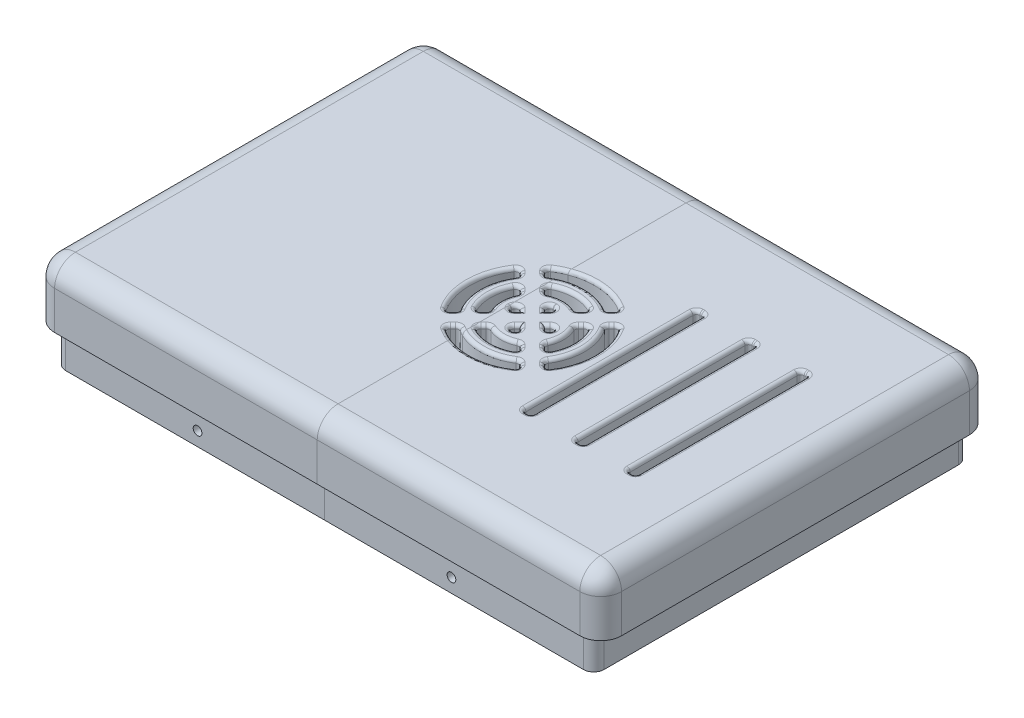
SolidWorks part; units mm, degrees
ref_plane "Plan de face" through (0, 0, 0) normal (0, 0, 1) x (1, 0, 0)
ref_plane "Plan de dessus" through (0, 0, 0) normal (0, 1, 0) x (1, 0, 0)
ref_plane "Plan de droite" through (0, 0, 0) normal (1, 0, 0) x (0, 0, -1)
sketch "Esquisse1" plane through (0, 0, 0) normal (0, 1, 0) x (1, 0, 0)
  line L1 (-81.5, 56) -> (81.5, 56)
  line L2 (-81.5, 56) -> (-81.5, -56)
  line L3 (-81.5, -56) -> (81.5, -56)
  line L4 (81.5, 56) -> (81.5, -56)
  line L5 (-81.5, 56) -> (81.5, -56) construction
  line L6 (-81.5, -56) -> (81.5, 56) construction
  point P0 (0, 0)
  dimension "D1" = 112
  dimension "D2" = 163
extrude "General shape" add sketch "Esquisse1" along normal blind 7
sketch "Esquisse2" plane through (0, 0, 0) normal (0, -1, 0) x (1, 0, 0)
  line L1 (81.5, -56) -> (-81.5, -56)
  line L2 (81.5, -56) -> (81.5, 56)
  line L3 (81.5, 56) -> (-81.5, 56)
  line L4 (-81.5, -56) -> (-81.5, 56)
  line L5 (81.5, -56) -> (-81.5, 56) construction
  line L6 (81.5, 56) -> (-81.5, -56) construction
  line L7 (73.5, -51.5) -> (-73.5, -51.5)
  line L8 (73.5, -51.5) -> (73.5, 51.5)
  line L9 (73.5, 51.5) -> (-73.5, 51.5)
  line L10 (-73.5, -51.5) -> (-73.5, 51.5)
  line L11 (73.5, -51.5) -> (-73.5, 51.5) construction
  line L12 (73.5, 51.5) -> (-73.5, -51.5) construction
  point P0 (0, 0)
  point P7 (0, 0)
  dimension "D1" = 8
  dimension "D2" = 4.5
extrude "Boss.-Extru.2" add sketch "Esquisse2" along normal blind 20
sketch "Esquisse3" plane through (0, -20, 0) normal (0, -1, 0) x (-1, 0, 0)
  line L1 (-81.5, 56) -> (81.5, 56)
  line L2 (-81.5, 56) -> (-81.5, -56)
  line L3 (-81.5, -56) -> (81.5, -56)
  line L4 (81.5, 56) -> (81.5, -56)
  line L5 (-81.5, 56) -> (81.5, -56) construction
  line L6 (-81.5, -56) -> (81.5, 56) construction
  line L7 (-77.4, 53.9) -> (77.4, 53.9)
  line L8 (-77.4, 53.9) -> (-77.4, -53.9)
  line L9 (-77.4, -53.9) -> (77.4, -53.9)
  line L10 (77.4, 53.9) -> (77.4, -53.9)
  line L11 (-77.4, 53.9) -> (77.4, -53.9) construction
  line L12 (-77.4, -53.9) -> (77.4, 53.9) construction
  point P0 (0, 0)
  point P7 (0, 0)
  dimension "D1" = 2.1
  dimension "D2" = 4.1
extrude "Enlèv. mat.-Extru.1" cut sketch "Esquisse3" against normal blind 10
fillet "Fillet1" radius 6 4 edges at (81.5, -1.5, 56) (81.5, -1.5, -56) (-81.5, -1.5, -56) (-81.5, -1.5, 56)
fillet "Fillet2" radius 6 8 edges at (-79.7426, 7, 54.2426) (-81.5, 7, 0) (-79.7426, 7, -54.2426) (0, 7, -56) (79.7426, 7, -54.2426) (81.5, 7, 0) (79.7426, 7, 54.2426) (0, 7, 56)
fillet "Fillet3" radius 3 4 edges at (73.5, 0, 0) (0, 0, -51.5) (-73.5, 0, 0) (0, 0, 51.5)
fillet "Fillet4" radius 3 4 edges at (-77.4, -15, 53.9) (77.4, -15, 53.9) (77.4, -15, -53.9) (-77.4, -15, -53.9)
sketch "Esquisse4" plane through (0, 0, 0) normal (0, -1, 0) x (1, 0, 0)
  line L0 (6.5, 0.67) -> (-6.2279, 13.3979) construction
  line L1 (-73, -51) -> (73, -51)
  line L2 (-73, -51) -> (-73, 51)
  line L3 (-73, 51) -> (73, 51)
  line L4 (73, -51) -> (73, 51)
  line L5 (-73, -51) -> (73, 51) construction
  line L6 (-73, 51) -> (73, -51) construction
  line L7 (-2.5, 0.67) -> (-5.5, 0.67) construction
  line L8 (-5.5, 0.67) -> (-8.5, 0.67) construction
  line L9 (-8.5, 0.67) -> (-11.5, 0.67) construction
  line L10 (-2.5, 0.67) -> (0.5, 0.67) construction
  line L11 (0.5, 0.67) -> (3.5, 0.67) construction
  line L12 (3.5, 0.67) -> (6.5, 0.67) construction
  line L13 (6.5, 0.67) -> (19.2279, 13.3979) construction
  line L14 (6.5, 0.67) -> (19.2279, -12.0579) construction
  line L15 (6.5, 0.67) -> (-6.2279, -12.0579) construction
  line L16 (25.9454, -22.311) -> (-16.481, 20.1154)
  line L17 (25.9454, -22.311) -> (29.481, -18.7754)
  line L18 (-16.481, 20.1154) -> (-12.9454, 23.651)
  line L19 (29.481, -18.7754) -> (-12.9454, 23.651)
  line L20 (25.9454, -22.311) -> (-12.9454, 23.651) construction
  line L21 (-16.481, 20.1154) -> (29.481, -18.7754) construction
  line L22 (-12.9454, -22.311) -> (29.481, 20.1154)
  line L23 (-12.9454, -22.311) -> (-16.481, -18.7754)
  line L24 (29.481, 20.1154) -> (25.9454, 23.651)
  line L25 (-16.481, -18.7754) -> (25.9454, 23.651)
  line L26 (-12.9454, -22.311) -> (25.9454, 23.651) construction
  line L27 (29.481, 20.1154) -> (-16.481, -18.7754) construction
  circle A0 centre (6.5, 0.67) radius 18
  circle A1 centre (6.5, 0.67) radius 15
  circle A2 centre (6.5, 0.67) radius 12
  circle A3 centre (6.5, 0.67) radius 9
  circle A4 centre (6.5, 0.67) radius 6
  circle A5 centre (6.5, 0.67) radius 3
  point P0 (0, 0)
  point P6 (6.5, 0.67)
  dimension "D1" = 102
  dimension "D2" = 146
  dimension "D3" = 66.5
  dimension "D4" = 51.67
  dimension "D5" = 3
  dimension "D6" = 5
extrude "Fan_extrusion" cut sketch "Esquisse4" against normal up to surface (7 mm away) contours L16 A4 L25 | A3 L16 A2 L25 | A1 L16 A0 L25 | A1 L22 A0 L16 | A3 L22 A2 L16 | L22 A4 L16 | A1 L19 A0 L22 | A3 L19 A2 L22 | L19 A4 L22 | L25 A4 L19 | A3 L25 A2 L19 | A1 L25 A0 L19 region at (6.5, 0, -14.7998) region at (21.9698, 0, 0.67) region at (6.5, 0, -9.4114) region at (-8.9698, 0, 0.67) region at (16.5814, 0, 0.67) region at (6.5, 0, -4.4228) region at (-3.5814, 0, 0.67) region at (6.5, 0, 16.1398) region at (11.5928, 0, 0.67) region at (1.4072, 0, 0.67) region at (6.5, 0, 10.7514) region at (6.5, 0, 5.7628) up to face at (0, 7, 0)
sketch "Esquisse5" plane through (0, 0, 0) normal (0, -1, 0) x (1, 0, 0)
  line L0 (6.5, 6.67) -> (6.5, -5.33) construction
  line L2 (22.55, -15.38) -> (-9.55, -15.38)
  line L3 (22.55, -15.38) -> (22.55, 16.72)
  line L4 (22.55, 16.72) -> (-9.55, 16.72)
  line L5 (-9.55, -15.38) -> (-9.55, 16.72)
  line L6 (22.55, -15.38) -> (-9.55, 16.72) construction
  line L7 (22.55, 16.72) -> (-9.55, -15.38) construction
  arc A0 (8.589, 6.2946) -> (4.411, 6.2946) centre (6.5, 0.67) ccw construction
  arc A1 (4.411, -4.9546) -> (8.589, -4.9546) centre (6.5, 0.67) ccw construction
  circle A3 centre (-9.55, 16.72) radius 1.25
  circle A4 centre (22.55, 16.72) radius 1.25
  circle A5 centre (22.55, -15.38) radius 1.25
  circle A6 centre (-9.55, -15.38) radius 1.25
  point P9 (6.5, 0.67)
  dimension "D3" = 2.5
  dimension "D1" = 32.1
  dimension "D2" = 32.1
extrude "Fan_scree_holes" cut sketch "Esquisse5" against normal blind 5 contours A3 | A6 | A4 | A5
fillet "Fan_fillet" radius 1 128 edges at (19.7992, 7, -9.0936) (19.7992, 7, 10.4336) (19.7992, 0, 10.4336) (19.7992, 0, -9.0936) (15.4741, 7, -4.7685) (15.4741, 7, 6.1085) (15.4741, 0, 6.1085) (15.4741, 0, -4.7685) (-3.2636, 7, -12.6292) (16.2636, 7, -12.6292) (16.2636, 0, -12.6292) (-3.2636, 0, -12.6292) (1.0615, 7, -8.3041) (11.9385, 7, -8.3041) (11.9385, 0, -8.3041) (1.0615, 0, -8.3041) (11.0801, 7, -0.3745) (11.0801, 7, 1.7145) (11.0801, 0, 1.7145) (11.0801, 0, -0.3745) (5.4555, 7, -3.9101) (7.5445, 7, -3.9101) (7.5445, 0, -3.9101) (5.4555, 0, -3.9101) (-6.7992, 7, 10.4336) (-6.7992, 7, -9.0936) (-6.7992, 0, -9.0936) (-6.7992, 0, 10.4336) (-2.4741, 7, 6.1085) (-2.4741, 7, -4.7685) (-2.4741, 0, -4.7685) (-2.4741, 0, 6.1085) (1.9199, 7, 1.7145) (1.9199, 7, -0.3745) (1.9199, 0, -0.3745) (1.9199, 0, 1.7145) (7.5445, 7, 5.2501) (5.4555, 7, 5.2501) (5.4555, 0, 5.2501) (7.5445, 0, 5.2501) (11.9385, 7, 9.6441) (1.0615, 7, 9.6441) (1.0615, 0, 9.6441) (11.9385, 0, 9.6441) (16.2636, 7, 13.9692) (-3.2636, 7, 13.9692) (-3.2636, 0, 13.9692) (16.2636, 0, 13.9692) (14.3813, 3.5, -3.6757) (15.5, 0, 0.67) (14.3813, 3.5, 5.0157) (15.5, 7, 0.67) (18.726, 3.5, -8.0205) (21.5, 0, 0.67) (18.726, 3.5, 9.3605) (21.5, 7, 0.67) (2.1543, 3.5, -7.2113) (6.5, 0, -8.33) (10.8457, 3.5, -7.2113) (6.5, 7, -8.33) (-2.1905, 3.5, -11.556) (6.5, 0, -14.33) (15.1905, 3.5, -11.556) (6.5, 7, -14.33) (24.5, 7, 0.67) (20.8723, 3.5, 11.5068) (24.5, 0, 0.67) (20.8723, 3.5, -10.1668) (18.5, 7, 0.67) (16.5669, 3.5, 7.2013) (18.5, 0, 0.67) (16.5669, 3.5, -5.8613) (6.5, 7, -17.33) (17.3368, 3.5, -13.7023) (6.5, 0, -17.33) (-4.3368, 3.5, -13.7023) (6.5, 7, -11.33) (13.0313, 3.5, -9.3969) (6.5, 0, -11.33) (-0.0313, 3.5, -9.3969) (12.5, 7, 0.67) (12.1246, 3.5, 2.759) (12.5, 0, 0.67) (12.1246, 3.5, -1.419) (6.5, 7, -5.33) (8.589, 3.5, -4.9546) (6.5, 0, -5.33) (4.411, 3.5, -4.9546) (-5.726, 3.5, 9.3605) (-8.5, 0, 0.67) (-5.726, 3.5, -8.0205) (-8.5, 7, 0.67) (-1.3813, 3.5, 5.0157) (-2.5, 0, 0.67) (-1.3813, 3.5, -3.6757) (-2.5, 7, 0.67) (-11.5, 7, 0.67) (-7.8723, 3.5, -10.1668) (-11.5, 0, 0.67) (-7.8723, 3.5, 11.5068) (-5.5, 7, 0.67) (-3.5669, 3.5, -5.8613) (-5.5, 0, 0.67) (-3.5669, 3.5, 7.2013) (0.5, 7, 0.67) (0.8754, 3.5, -1.419) (0.5, 0, 0.67) (0.8754, 3.5, 2.759) (6.5, 7, 6.67) (4.411, 3.5, 6.2946) (6.5, 0, 6.67) (8.589, 3.5, 6.2946) (15.1905, 3.5, 12.896) (6.5, 0, 15.67) (-2.1905, 3.5, 12.896) (6.5, 7, 15.67) (10.8457, 3.5, 8.5513) (6.5, 0, 9.67) (2.1543, 3.5, 8.5513) (6.5, 7, 9.67) (6.5, 7, 12.67) (-0.0313, 3.5, 10.7369) (6.5, 0, 12.67) (13.0313, 3.5, 10.7369) (6.5, 7, 18.67) (-4.3368, 3.5, 15.0423) (6.5, 0, 18.67) (17.3368, 3.5, 15.0423)
sketch "Esquisse8" plane through (0, 7, 0) normal (0, 1, 0) x (1, 0, 0)
  line L0 (-75.5, 0) -> (75.5, 0) construction
  line L1 (-75.5, 50) -> (-75.5, -50) construction
  line L2 (75.5, -50) -> (75.5, 50) construction
  line L3 (43, -25) -> (45.5, -25)
  line L10 (58, -25) -> (60.5, -25)
  line L11 (58, -25) -> (58, 25)
  line L12 (58, 25) -> (60.5, 25)
  line L13 (60.5, -25) -> (60.5, 25)
  line L14 (58, -25) -> (60.5, 25) construction
  line L15 (58, 25) -> (60.5, -25) construction
  line L16 (43, -25) -> (43, 25)
  line L17 (45.5, -25) -> (45.5, 25)
  line L18 (43, 25) -> (45.5, 25)
  line L19 (28, -25) -> (30.5, -25)
  line L20 (28, -25) -> (28, 25)
  line L21 (30.5, -25) -> (30.5, 25)
  line L22 (28, 25) -> (30.5, 25)
  point P11 (59.25, 0)
  dimension "D4" = 50
  dimension "D5" = 2.5
  dimension "D6" = 15
  dimension "D7" = 3
extrude "Passive_air_extrusion" cut sketch "Esquisse8" against normal up to surface (7 mm away) up to face at (11.3437, 0, 0.67)
fillet "Passive_air_extrusion_fillet" radius 1 36 edges at (29.25, 0, 25) (29.25, 7, 25) (59.25, 7, 25) (59.25, 0, 25) (58, 3.5, 25) (58, 7, 0) (58, 0, 0) (44.25, 7, 25) (44.25, 0, 25) (43, 3.5, 25) (43, 7, 0) (43, 0, 0) (60.5, 7, 0) (60.5, 3.5, 25) (60.5, 0, 0) (58, 3.5, -25) (59.25, 7, -25) (60.5, 3.5, -25) (59.25, 0, -25) (45.5, 7, 0) (45.5, 3.5, 25) (45.5, 0, 0) (43, 3.5, -25) (44.25, 7, -25) (45.5, 3.5, -25) (44.25, 0, -25) (30.5, 7, 0) (30.5, 3.5, 25) (30.5, 0, 0) (29.25, 7, -25) (30.5, 3.5, -25) (29.25, 0, -25) (28, 3.5, 25) (28, 7, 0) (28, 3.5, -25) (28, 0, 0)
ref_plane "Plane" through (0, 0, 0) normal (1, 0, 0) x (0, 0, -1)
split "Middle_split" trim tools "Plane" bodies to split 109 resulting bodies 112 113
sketch "Esquisse9" plane through (0, 0, 53.9) normal (0, 0, 1) x (1, 0, 0)
  circle A0 centre (-36.5, -16) radius 1.25
  circle A1 centre (36.5, -16) radius 1.25
  dimension "D1" = 2.5
extrude "Closing_screw_holes" cut sketch "Esquisse9" against normal through all
